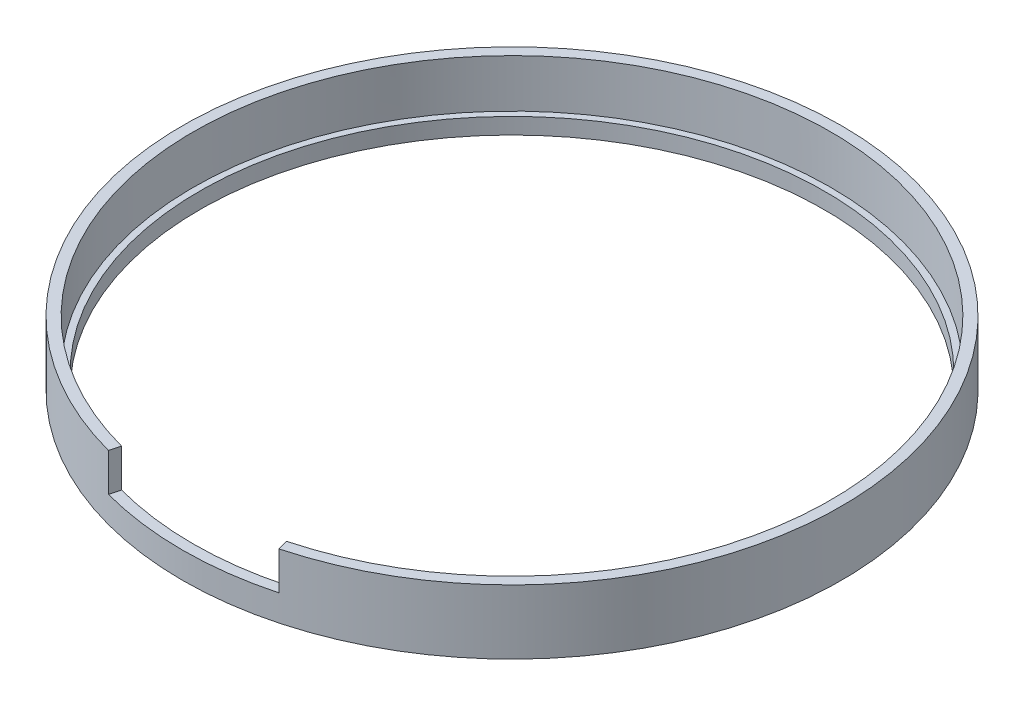
SolidWorks part; units mm, degrees
ref_plane "前视基准面" through (0, 0, 0) normal (0, 0, 1) x (1, 0, 0)
ref_plane "上视基准面" through (0, 0, 0) normal (0, 1, 0) x (1, 0, 0)
ref_plane "右视基准面" through (0, 0, 0) normal (1, 0, 0) x (0, 0, -1)
sketch "草图1" plane through (0, 0, 0) normal (0, 1, 0) x (1, 0, 0)
  circle A0 centre (0, 0) radius 200
  circle A1 centre (0, 0) radius 189.6
  circle A2 centre (0, 0) radius 193.5
  circle A3 centre (0, 0) radius 189.4
  dimension "D1" = 378.8
  dimension "D2" = 400
  dimension "D3" = 387
extrude "凸台-拉伸1" add sketch "草图1" along normal blind 39 contours A0 | A2
extrude "凸台-拉伸2" add sketch "草图1<5>" along normal blind 9.8 contours A2 | A1
sketch "草图1<5>" plane through (0, 0, 0) normal (0, 1, 0) x (1, 0, 0) same geometry as "草图1"
sketch "草图4" plane through (0, 39, 0) normal (0, 1, 0) x (1, 0, 0)
  line L0 (-50.0815, -186.9066) -> (-51.7638, -193.1852)
  line L1 (50.0815, -186.9066) -> (51.7638, -193.1852)
  line L2 (0, 0) -> (0, -264.9327) construction
  circle A0 centre (0, 0) radius 193.5 construction
  circle A1 centre (0, 0) radius 200 construction
  arc A2 (-50.0815, -186.9066) -> (50.0815, -186.9066) centre (0, 0) ccw
  arc A3 (-51.7638, -193.1852) -> (51.7638, -193.1852) centre (0, 0) ccw
  dimension "D1" = 15
  dimension "D2" = 15
extrude "切除-拉伸1" cut sketch "草图4" against normal up to surface (23.1 mm away)
